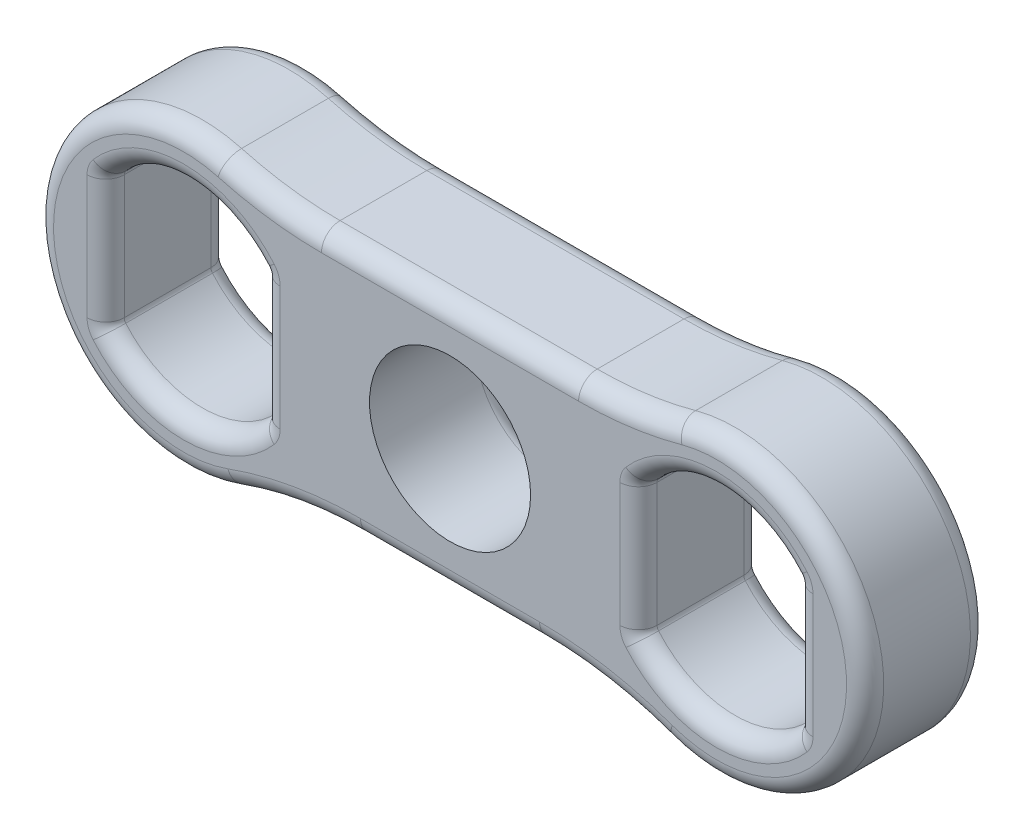
SolidWorks part; units mm, degrees
ref_plane "Płaszczyzna przednia" through (0, 0, 0) normal (0, 0, 1) x (1, 0, 0)
ref_plane "Płaszczyzna górna" through (0, 0, 0) normal (0, 1, 0) x (1, 0, 0)
ref_plane "Płaszczyzna prawa" through (0, 0, 0) normal (1, 0, 0) x (0, 0, -1)
sketch "Szkic1" plane through (0, 0, 0) normal (0, 1, 0) x (1, 0, 0)
  line L0 (0, 0) -> (0, 2.6925)
  line L1 (15.4, -5) -> (-15.4, -5)
  line L2 (15.4, -5) -> (15.4, 5)
  line L3 (15.4, 5) -> (-15.4, 5)
  line L4 (-15.4, -5) -> (-15.4, 5)
  line L5 (15.4, -5) -> (-15.4, 5) construction
  line L6 (15.4, 5) -> (-15.4, -5) construction
  line L7 (-15.4, -5) -> (-27.9, -5)
  line L8 (-15.4, -5) -> (-15.4, 5)
  line L9 (-15.4, 5) -> (-27.9, 5)
  line L10 (-27.9, -5) -> (-27.9, 5)
  line L11 (-27.9, -5) -> (-32.9, -5)
  line L12 (-27.9, -5) -> (-27.9, 5)
  line L13 (-27.9, 5) -> (-32.9, 5)
  line L14 (-32.9, -5) -> (-32.9, 5)
  line L15 (27.9, 5) -> (32.9, 5)
  line L16 (32.9, -5) -> (32.9, 5)
  line L17 (27.9, -5) -> (32.9, -5)
  line L18 (27.9, -5) -> (27.9, 5)
  line L19 (15.4, 5) -> (27.9, 5)
  line L20 (27.9, -5) -> (27.9, 5)
  line L21 (15.4, -5) -> (27.9, -5)
  line L22 (15.4, -5) -> (15.4, 5)
  point P0 (0, 0)
  dimension "D1" = 12.5
  dimension "D2" = 30.8
  dimension "D3" = 12.5
  dimension "D4" = 5
  dimension "D5" = 10
extrude "Dodanie-wyciągnięcie1" add sketch "Szkic1" along normal blind 20 contours L14 L11 L10 L13 | L10 L7 L4 L9 | L4 L1 L2 L3 | L2 L21 L18 L19 | L18 L17 L16 L15 region at (0, 0, 4.6762) region at (21.65, 0, 0) region at (-21.65, 0, 0) region at (30.4, 0, 0) region at (-30.4, 0, 0)
sketch "Szkic3" plane through (0, 0, -5) normal (0, 0, -1) x (-1, 0, 0)
  line L0 (0, 20) -> (0, 0)
  line L1 (-32.9, 20) -> (32.9, 20) construction
  line L2 (0, 10) -> (-15.25, 10)
  line L3 (-15.25, 10) -> (-27.75, 10)
  line L4 (-27.75, 10) -> (-32.9, 10)
  line L5 (-32.9, 20) -> (-32.9, 0) construction
  line L6 (-27.75, 10) -> (-27.75, 17.0733) construction
  line L7 (-27.75, 17.0733) -> (-27.75, 10) construction
  line L8 (-27.75, 3.2789) -> (-27.75, 10) construction
  line L9 (-27.75, 16.7211) -> (-27.75, 3.2789)
  line L10 (-15.25, 2.9267) -> (-15.25, 17.0733)
  line L11 (27.75, 3.2789) -> (27.75, 10) construction
  line L12 (27.75, 17.0733) -> (27.75, 10) construction
  line L13 (-21.5, 10) -> (-21.5, 9.5)
  line L14 (27.75, 10) -> (27.75, 17.0733) construction
  line L15 (21.5, 10) -> (21.5, 9.5)
  line L16 (15.25, 2.9267) -> (15.25, 17.0733)
  line L17 (27.75, 16.7211) -> (27.75, 3.2789)
  line L18 (27.75, 10) -> (32.9, 10)
  line L19 (15.25, 10) -> (27.75, 10)
  circle A6 centre (0, 10) radius 6.5
  circle A7 centre (-21.5, 9.5) radius 8.25
  circle A9 centre (-21.5, 9.5) radius 18
  circle A10 centre (21.5, 9.5) radius 18
  circle A11 centre (21.5, 9.5) radius 8.25
  circle A13 centre (-21.5, 9.5) radius 12
  circle A14 centre (21.5, 9.5) radius 12
  point P25 (-27.75, 10)
  point P27 (-15.25, 10)
  point P37 (15.25, 10)
  point P38 (27.75, 10)
  dimension "D1" = 15.25
  dimension "D2" = 12.5
  dimension "D3" = 5.15
extrude "Dodanie-wyciągnięcie2" add sketch "Szkic3" along normal up to surface (-10 mm away) from surface separate body up to face at (0, 10, 5) starting at face at (0, 10, -5)
sketch "Szkic4" plane through (0, 0, -5) normal (0, 0, -1) x (-1, 0, 0)
  line L0 (0, 20) -> (0, 0)
  line L1 (-32.9, 20) -> (32.9, 20) construction
  line L2 (-15.2067, 9.5) -> (-27.7933, 9.5)
  line L3 (-27.7933, 3.1882) -> (-27.7933, 15.8118)
  line L4 (-15.2067, 2.5093) -> (-15.2067, 16.4907)
  line L5 (-27.7933, 4.3215) -> (-15.2067, 4.3215)
  line L6 (15.2067, 3.6247) -> (15.2067, 15.3753)
  line L7 (27.7933, 2.8973) -> (27.7933, 16.1027)
  line L8 (-21.5, 10) -> (-21.5, 9.5) construction
  line L9 (-32.9, 20) -> (-21.5, 10) construction
  line L10 (15.2067, 9.5) -> (27.7933, 9.5)
  line L11 (-21.5, 10) -> (-21.5, 20) construction
  line L12 (-15.6905, 20) -> (-27.3095, 20) construction
  circle A3 centre (0, 10) radius 6.5
  circle A7 centre (-21.5, 9.5) radius 12
  circle A8 centre (-21.5, 9.5) radius 8.15
  circle A9 centre (-21.5, 9.5) radius 18
  circle A10 centre (21.5, 9.5) radius 18
  circle A11 centre (21.5, 9.5) radius 12
  circle A12 centre (21.5, 9.5) radius 8.15
  point P12 (-21.5, 9.5)
  point P18 (-21.5, 10)
  point P25 (-15.2067, 10)
  point P27 (-27.7933, 9.5)
  point P28 (-15.2067, 9.5)
  point P35 (15.2067, 9.5)
  point P38 (27.7933, 9.5)
  line M7 (-32.9, 0) -> (32.9, 0)
  line M8 (32.9, 0) -> (32.9, 20)
  line M9 (32.9, 20) -> (-32.9, 20)
  line M10 (-32.9, 20) -> (-32.9, 0)
extrude "Wytnij-wyciągnięcie3" cut sketch "Szkic4" against normal blind 19 contours A7 M9 M10 | A7 M10 M7 | A8 L2 | L5 L2 | L5 A8 | A3 A9 | A9 A3 L0 | A3 A10 L0 | A10 A3 | A12 L10 | A12 L10 | A11 M9 M8 | A11 M8 M7 region at (-1.8224, 10.0503, -5) region at (1.8224, 10.0503, -5) region at (-4.8612, 9.8869, -5) region at (4.8612, 9.8869, -5) region at (-31.2721, 18.0675, -5) region at (31.2721, 18.0675, -5) region at (-31.6807, 1.691, -5) region at (31.6807, 1.691, -5) region at (21.5, 6.9107, -5) region at (21.5, 13.1728, -5) region at (21.5, 3.1121, -5) region at (-21.5, 5.8272, -5) region at (-21.5, 13.1728, -5)
combine bodies "Połącz2" operation type add bodies to combine 142 138 140 139 111 110 109
fillet "Zaokrąglenie1" radius 30 4 edges at (-14.1686, 0, 0) (14.1686, 0, 0) (15.6905, 20, 0) (-15.6905, 20, 0)
fillet "Zaokrąglenie2" radius 0.5 8 edges at (-27.7933, 4.3215, 0) (-27.7933, 14.6785, 0) (-15.2067, 14.6785, 0) (-15.2067, 4.3215, 0) (15.2067, 4.3215, 0) (15.2067, 14.6785, 0) (27.7933, 4.3215, 0) (27.7933, 14.6785, 0)
fillet "Zaokrąglenie3" radius 1.5 49 edges at (0, 20, -5) (-14.3846, 20.2691, -5) (-33.4907, 9.0279, -5) (-12.4014, -0.4498, -5) (0, 0, -5) (12.4014, -0.4498, -5) (33.4907, 9.0279, -5) (33.4907, 9.0279, 5) (12.4014, -0.4498, 5) (0, 0, 5) (-12.4014, -0.4498, 5) (-33.4907, 9.0279, 5) (-14.3846, 20.2691, 5) (0, 20, 5) (27.762, 14.6702, 5) (27.7933, 9.5, 5) (27.762, 4.3298, 5) (21.5, 1.35, 5) (15.238, 4.3298, 5) (15.2067, 9.5, 5) (15.238, 14.6702, 5) (-15.238, 14.6702, 5) (-21.5, 17.65, 5) (-27.762, 14.6702, 5) (-27.7933, 9.5, 5) (-27.762, 4.3298, 5) (-21.5, 1.35, 5) (-15.238, 4.3298, 5) (-15.238, 14.6702, -5) (-15.2067, 9.5, -5) (-15.238, 4.3298, -5) (-21.5, 1.35, -5) (-27.762, 4.3298, -5) (-27.7933, 9.5, -5) (-27.762, 14.6702, -5) (15.238, 14.6702, -5) (15.2067, 9.5, -5) (15.238, 4.3298, -5) (21.5, 1.35, -5) (27.762, 4.3298, -5) (27.7933, 9.5, -5) (27.762, 14.6702, -5) (14.3846, 20.2691, -5) (14.3846, 20.2691, 5) (-6.5, 10, -5) (21.5, 17.65, 5) (-15.2067, 9.5, 5) (-21.5, 17.65, -5) (21.5, 17.65, -5)
